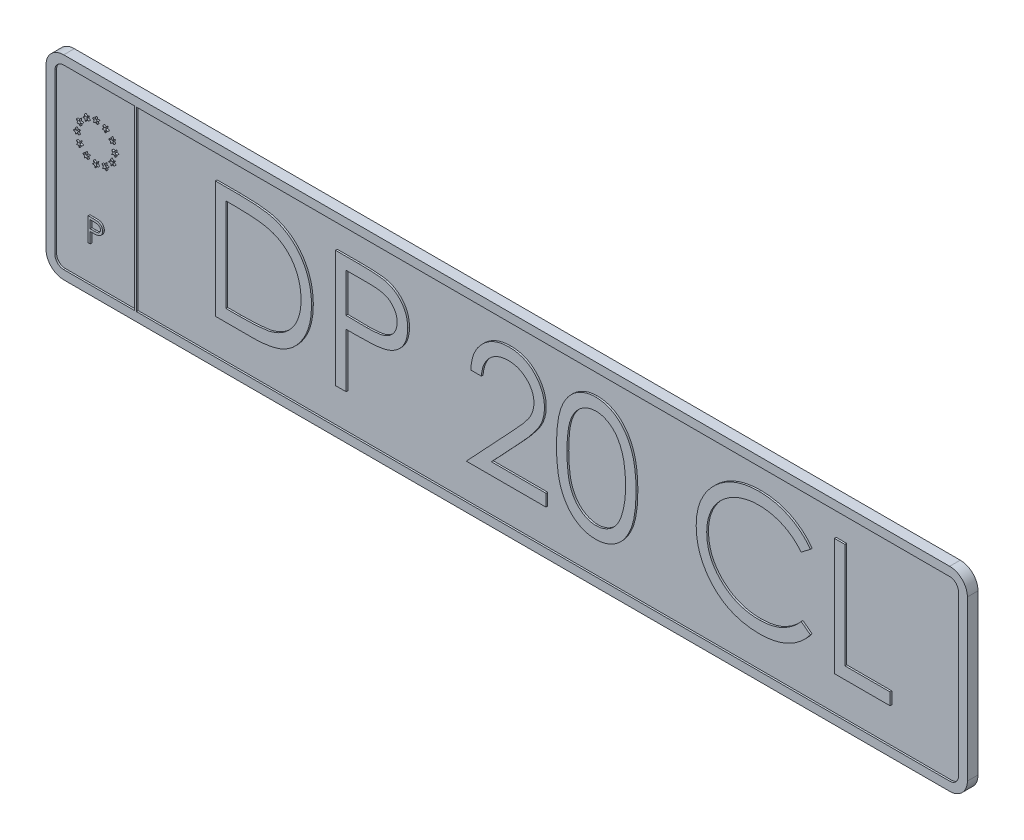
SolidWorks part; units mm, degrees
ref_plane "Front Plane" through (0, 0, 0) normal (0, 0, 1) x (1, 0, 0)
ref_plane "Top Plane" through (0, 0, 0) normal (0, 1, 0) x (1, 0, 0)
ref_plane "Right Plane" through (0, 0, 0) normal (1, 0, 0) x (0, 0, -1)
sketch "Sketch1" plane through (0, 0, 0) normal (0, 0, 1) x (1, 0, 0)
  line L1 (10, 0) -> (510, 0)
  line L2 (0, -10) -> (0, -100)
  line L3 (10, -110) -> (510, -110)
  line L4 (520, -10) -> (520, -100)
  arc A0 (510, 0) -> (520, -10) centre (510, -10) cw
  arc A1 (520, -100) -> (510, -110) centre (510, -100) cw
  arc A2 (10, -110) -> (0, -100) centre (10, -100) cw
  arc A3 (0, -10) -> (10, 0) centre (10, -10) cw
  point P7 (520, 0)
  point P12 (0, -110)
  point P15 (0, 0)
  dimension "D3" = 10
  dimension "D1" = 520
  dimension "D2" = 110
extrude "Boss-Extrude1" add sketch "Sketch1" along normal blind 5
sketch "Sketch2" plane through (0, 0, 5) normal (0, 0, 1) x (1, 0, 0)
  line L8 (510, -5) -> (10, -5)
  line L9 (5, -10) -> (5, -100)
  line L10 (10, -105) -> (510, -105)
  line L11 (515, -100) -> (515, -10)
  line L12 (510, -5) -> (10, -5)
  line L13 (5, -10) -> (5, -100)
  line L14 (10, -105) -> (510, -105)
  line L15 (515, -100) -> (515, -10)
  line L16 (510, 0) -> (10, 0)
  line L17 (0, -10) -> (0, -100)
  line L18 (10, -110) -> (510, -110)
  line L19 (520, -100) -> (520, -10)
  line L20 (510, 0) -> (10, 0)
  line L21 (0, -10) -> (0, -100)
  line L22 (10, -110) -> (510, -110)
  line L23 (520, -100) -> (520, -10)
  arc A8 (515, -10) -> (510, -5) centre (510, -10) ccw
  arc A9 (10, -5) -> (5, -10) centre (10, -10) ccw
  arc A10 (5, -100) -> (10, -105) centre (10, -100) ccw
  arc A11 (510, -105) -> (515, -100) centre (510, -100) ccw
  arc A12 (515, -10) -> (510, -5) centre (510, -10) ccw
  arc A13 (10, -5) -> (5, -10) centre (10, -10) ccw
  arc A14 (5, -100) -> (10, -105) centre (10, -100) ccw
  arc A15 (510, -105) -> (515, -100) centre (510, -100) ccw
  arc A16 (520, -10) -> (510, 0) centre (510, -10) ccw
  arc A17 (10, 0) -> (0, -10) centre (10, -10) ccw
  arc A18 (0, -100) -> (10, -110) centre (10, -100) ccw
  arc A19 (510, -110) -> (520, -100) centre (510, -100) ccw
  arc A20 (520, -10) -> (510, 0) centre (510, -10) ccw
  arc A21 (10, 0) -> (0, -10) centre (10, -10) ccw
  arc A22 (0, -100) -> (10, -110) centre (10, -100) ccw
  arc A23 (510, -110) -> (520, -100) centre (510, -100) ccw
  dimension "D1" = 5
  dimension "D2" = 0
extrude "Boss-Extrude2" add sketch "Sketch2" along normal blind 1
sketch "Sketch3" plane through (0, 0, 5) normal (0, 0, 1) x (1, 0, 0)
  line L0 (510, -5) -> (10, -5) construction
  line L3 (51, -5) -> (50, -5)
  line L4 (51, -5) -> (51, -105)
  line L5 (51, -105) -> (50, -105)
  line L6 (50, -5) -> (50, -105)
  line L7 (10, -105) -> (510, -105) construction
  line L8 (5, -10) -> (5, -100) construction
  dimension "D1" = 1
  dimension "D2" = 45
extrude "Boss-Extrude4" add sketch "Sketch3" along normal up to surface (1 mm away) up to face at (260, -55, 6)
sketch "Sketch10" plane through (0, 0, 5) normal (0, 0, 1) x (1, 0, 0)
  line L0 (5, -85) -> (50, -85) construction
  line L1 (5, -10) -> (5, -100) construction
  line L2 (50, -5) -> (50, -105) construction
  line L3 (10, -105) -> (50, -105) construction
  text T0 "P" font "Century Gothic" height in points 50
  dimension "D1" = 20
extrude "Boss-Extrude9" add sketch "Sketch10" along normal blind 1
sketch "Sketch9" plane through (0, 0, 5) normal (0, 0, 1) x (1, 0, 0)
  line L0 (51, -85) -> (515, -85) construction
  line L1 (51, -105) -> (51, -5) construction
  line L2 (515, -100) -> (515, -10) construction
  line L3 (10, -110) -> (510, -110) construction
  text T0 "DP 20 CL\r\n" font "Century Gothic" height in points 250
  dimension "D1" = 25
extrude "Boss-Extrude8" add sketch "Sketch9" along normal blind 1
sketch "Sketch14" plane through (0, 0, 5) normal (0, 0, 1) x (1, 0, 0)
  line L0 (225.9935, 574.8658) -> (1025.9935, 574.8658) construction
  line L1 (26.2061, -22.8068) -> (27.4265, -22.8068)
  line L2 (27.4265, -22.8068) -> (27.7889, -21.6343)
  line L3 (27.7889, -21.6343) -> (28.2188, -22.8068)
  line L4 (28.2188, -22.8068) -> (29.4597, -22.8068)
  line L5 (29.4597, -22.8068) -> (28.4655, -23.52)
  line L6 (28.4655, -23.52) -> (28.8492, -24.7542)
  line L7 (28.8492, -24.7542) -> (27.7889, -24.0205)
  line L8 (27.7889, -24.0205) -> (26.7662, -24.7542)
  line L9 (26.7662, -24.7542) -> (27.1478, -23.52)
  line L10 (27.1478, -23.52) -> (26.2061, -22.8068)
  line L11 (33.0819, -24.1279) -> (33.982, -23.2937)
  line L12 (33.982, -23.2937) -> (33.7681, -24.5241)
  line L13 (33.7681, -24.5241) -> (34.8427, -25.1445)
  line L14 (34.8427, -25.1445) -> (33.6251, -25.2651)
  line L15 (33.6251, -25.2651) -> (33.3403, -26.5258)
  line L16 (33.3403, -26.5258) -> (32.7889, -25.3602)
  line L17 (32.7889, -25.3602) -> (31.5364, -25.4843)
  line L18 (31.5364, -25.4843) -> (32.4839, -24.6063)
  line L19 (32.4839, -24.6063) -> (32.025, -23.5177)
  line L20 (32.025, -23.5177) -> (33.0819, -24.1279)
  line L21 (37.319, -28.0997) -> (38.5157, -27.8274)
  line L22 (38.5157, -27.8274) -> (37.7152, -28.7859)
  line L23 (37.7152, -28.7859) -> (38.3357, -29.8606)
  line L24 (38.3357, -29.8606) -> (37.2209, -29.3562)
  line L25 (37.2209, -29.3562) -> (36.3439, -30.3055)
  line L26 (36.3439, -30.3055) -> (36.4492, -29.0205)
  line L27 (36.4492, -29.0205) -> (35.3024, -28.5017)
  line L28 (35.3024, -28.5017) -> (36.562, -28.215)
  line L29 (36.562, -28.215) -> (36.7088, -27.0428)
  line L30 (36.7088, -27.0428) -> (37.319, -28.0997)
  line L31 (39.0026, -33.658) -> (40.1751, -34.0205)
  line L32 (40.1751, -34.0205) -> (39.0026, -34.4504)
  line L33 (39.0026, -34.4504) -> (39.0026, -35.6913)
  line L34 (39.0026, -35.6913) -> (38.2894, -34.6971)
  line L35 (38.2894, -34.6971) -> (37.0552, -35.0807)
  line L36 (37.0552, -35.0807) -> (37.7889, -34.0205)
  line L37 (37.7889, -34.0205) -> (37.0552, -32.9978)
  line L38 (37.0552, -32.9978) -> (38.2894, -33.3793)
  line L39 (38.2894, -33.3793) -> (39.0026, -32.4376)
  line L40 (39.0026, -32.4376) -> (39.0026, -33.658)
  line L41 (37.6815, -39.3134) -> (38.5157, -40.2136)
  line L42 (38.5157, -40.2136) -> (37.2853, -39.9996)
  line L43 (37.2853, -39.9996) -> (36.6649, -41.0743)
  line L44 (36.6649, -41.0743) -> (36.5443, -39.8567)
  line L45 (36.5443, -39.8567) -> (35.2836, -39.5718)
  line L46 (35.2836, -39.5718) -> (36.4492, -39.0205)
  line L47 (36.4492, -39.0205) -> (36.3251, -37.768)
  line L48 (36.3251, -37.768) -> (37.2032, -38.7154)
  line L49 (37.2032, -38.7154) -> (38.2917, -38.2566)
  line L50 (38.2917, -38.2566) -> (37.6815, -39.3134)
  line L51 (33.7097, -43.5506) -> (33.982, -44.7472)
  line L52 (33.982, -44.7472) -> (33.0235, -43.9468)
  line L53 (33.0235, -43.9468) -> (31.9488, -44.5672)
  line L54 (31.9488, -44.5672) -> (32.4532, -43.4525)
  line L55 (32.4532, -43.4525) -> (31.5039, -42.5754)
  line L56 (31.5039, -42.5754) -> (32.7889, -42.6807)
  line L57 (32.7889, -42.6807) -> (33.3077, -41.534)
  line L58 (33.3077, -41.534) -> (33.5944, -42.7936)
  line L59 (33.5944, -42.7936) -> (34.7666, -42.9404)
  line L60 (34.7666, -42.9404) -> (33.7097, -43.5506)
  line L61 (28.1514, -45.2342) -> (27.7889, -46.4067)
  line L62 (27.7889, -46.4067) -> (27.359, -45.2342)
  line L63 (27.359, -45.2342) -> (26.1181, -45.2342)
  line L64 (26.1181, -45.2342) -> (27.1123, -44.5209)
  line L65 (27.1123, -44.5209) -> (26.7287, -43.2868)
  line L66 (26.7287, -43.2868) -> (27.7889, -44.0205)
  line L67 (27.7889, -44.0205) -> (28.8116, -43.2868)
  line L68 (28.8116, -43.2868) -> (28.4301, -44.5209)
  line L69 (28.4301, -44.5209) -> (29.3718, -45.2342)
  line L70 (29.3718, -45.2342) -> (28.1514, -45.2342)
  line L71 (22.496, -43.9131) -> (21.5958, -44.7472)
  line L72 (21.5958, -44.7472) -> (21.8098, -43.5169)
  line L73 (21.8098, -43.5169) -> (20.7351, -42.8964)
  line L74 (20.7351, -42.8964) -> (21.9527, -42.7758)
  line L75 (21.9527, -42.7758) -> (22.2376, -41.5152)
  line L76 (22.2376, -41.5152) -> (22.7889, -42.6807)
  line L77 (22.7889, -42.6807) -> (24.0414, -42.5567)
  line L78 (24.0414, -42.5567) -> (23.094, -43.4347)
  line L79 (23.094, -43.4347) -> (23.5529, -44.5233)
  line L80 (23.5529, -44.5233) -> (22.496, -43.9131)
  line L81 (18.2588, -39.9412) -> (17.0622, -40.2136)
  line L82 (17.0622, -40.2136) -> (17.8626, -39.255)
  line L83 (17.8626, -39.255) -> (17.2422, -38.1804)
  line L84 (17.2422, -38.1804) -> (18.357, -38.6847)
  line L85 (18.357, -38.6847) -> (19.234, -37.7354)
  line L86 (19.234, -37.7354) -> (19.1287, -39.0205)
  line L87 (19.1287, -39.0205) -> (20.2754, -39.5393)
  line L88 (20.2754, -39.5393) -> (19.0158, -39.826)
  line L89 (19.0158, -39.826) -> (18.869, -40.9981)
  line L90 (18.869, -40.9981) -> (18.2588, -39.9412)
  line L91 (16.5752, -34.3829) -> (15.4027, -34.0205)
  line L92 (15.4027, -34.0205) -> (16.5752, -33.5906)
  line L93 (16.5752, -33.5906) -> (16.5752, -32.3497)
  line L94 (16.5752, -32.3497) -> (17.2885, -33.3439)
  line L95 (17.2885, -33.3439) -> (18.5226, -32.9602)
  line L96 (18.5226, -32.9602) -> (17.7889, -34.0205)
  line L97 (17.7889, -34.0205) -> (18.5226, -35.0432)
  line L98 (18.5226, -35.0432) -> (17.2885, -34.6616)
  line L99 (17.2885, -34.6616) -> (16.5752, -35.6033)
  line L100 (16.5752, -35.6033) -> (16.5752, -34.3829)
  line L101 (17.8963, -28.7275) -> (17.0622, -27.8274)
  line L102 (17.0622, -27.8274) -> (18.2925, -28.0413)
  line L103 (18.2925, -28.0413) -> (18.913, -26.9667)
  line L104 (18.913, -26.9667) -> (19.0336, -28.1843)
  line L105 (19.0336, -28.1843) -> (20.2942, -28.4692)
  line L106 (20.2942, -28.4692) -> (19.1287, -29.0205)
  line L107 (19.1287, -29.0205) -> (19.2528, -30.273)
  line L108 (19.2528, -30.273) -> (18.3747, -29.3255)
  line L109 (18.3747, -29.3255) -> (17.2861, -29.7844)
  line L110 (17.2861, -29.7844) -> (17.8963, -28.7275)
  line L111 (21.8682, -24.4904) -> (21.5958, -23.2937)
  line L112 (21.5958, -23.2937) -> (22.5544, -24.0942)
  line L113 (22.5544, -24.0942) -> (23.629, -23.4737)
  line L114 (23.629, -23.4737) -> (23.1247, -24.5885)
  line L115 (23.1247, -24.5885) -> (24.074, -25.4655)
  line L116 (24.074, -25.4655) -> (22.7889, -25.3602)
  line L117 (22.7889, -25.3602) -> (22.2701, -26.507)
  line L118 (22.2701, -26.507) -> (21.9834, -25.2474)
  line L119 (21.9834, -25.2474) -> (20.8113, -25.1006)
  line L120 (20.8113, -25.1006) -> (21.8682, -24.4904)
  line L121 (27.7889, -34.0205) -> (26.7662, -24.7542) construction
  point P16 (27.7889, -34.0205)
  dimension "D1" = 10
  dimension "D2" = 9.3225
extrude "Boss-Extrude10" add sketch "Sketch14" along normal blind 1
